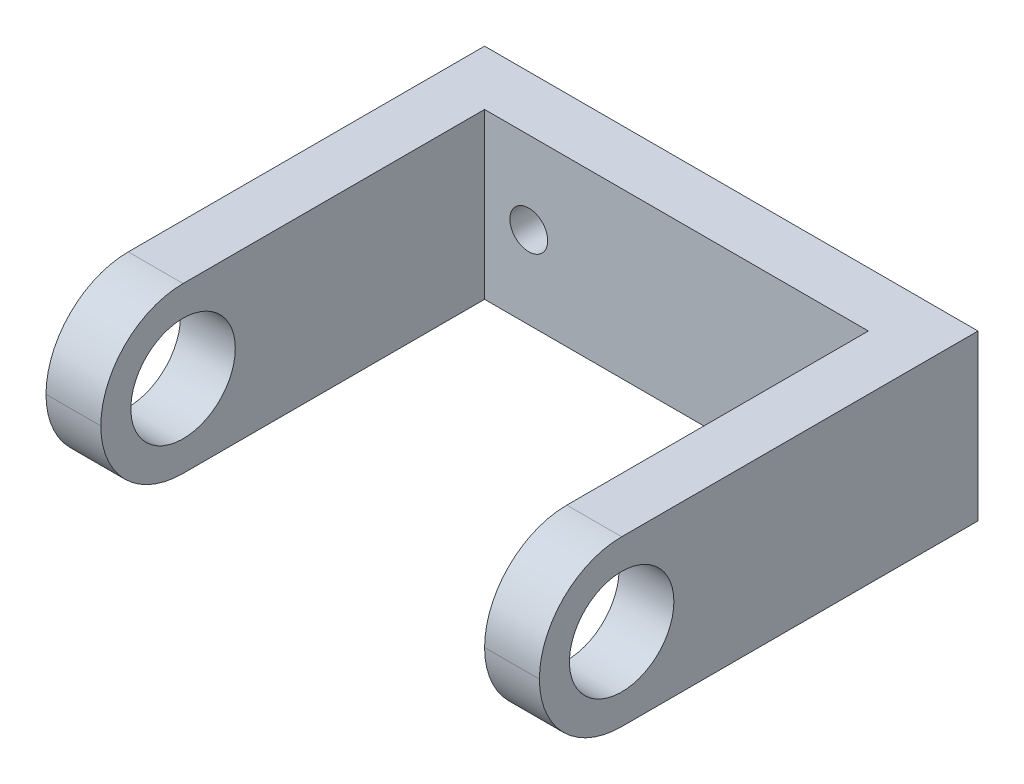
SolidWorks part; units mm, degrees
material "6061 Alloy"
ref_plane "Front Plane" through (0, 0, 0) normal (0, 0, 1) x (1, 0, 0)
ref_plane "Top Plane" through (0, 0, 0) normal (0, 1, 0) x (1, 0, 0)
ref_plane "Right Plane" through (0, 0, 0) normal (1, 0, 0) x (0, 0, -1)
sketch "Sketch1" plane through (0, 0, 0) normal (0, 1, 0) x (1, 0, 0)
  line L0 (-17.5, -7.5) -> (-22.5, -7.5)
  line L1 (-22.5, -7.5) -> (-22.5, 32.5)
  line L3 (-22.5, 32.5) -> (22.5, 32.5)
  line L5 (22.5, 32.5) -> (22.5, -7.5)
  line L6 (22.5, -7.5) -> (17.5, -7.5)
  line L7 (17.5, -7.5) -> (17.5, 27.5)
  line L9 (17.5, 27.5) -> (-17.5, 27.5)
  line L11 (-17.5, 27.5) -> (-17.5, -7.5)
  line L16 (0, 27.5) -> (0, 32.5) construction
  point P5 (0, 27.5)
  dimension "D1" = 5
  dimension "D2" = 35
  dimension "D3" = 27.5
  dimension "D6" = 7.5
extrude "Boss-Extrude1" add sketch "Sketch1" along normal mid plane 15
sketch "Sketch3" plane through (0, 0, 0) normal (1, 0, 0) x (0, 0, -1)
  circle A0 centre (0, 0) radius 4.7625
  dimension "D1" = 9.525
extrude "Cut-Extrude1" cut sketch "Sketch3" against normal through all both and the other way through all
fillet "Fillet1" radius 7.5 4 edges at (20, 7.5, 7.5) (20, -7.5, 7.5) (-20, -7.5, 7.5) (-20, 7.5, 7.5)
hole_wizard "#8-32 Tapped Hole1" positions "Sketch4" profile "Sketch5" tap size "#8-32" standard "ANSI Inch" end condition through all
sketch "Sketch4" plane through (0, 0, -27.5) normal (0, 0, 1) x (1, 0, 0)
  point P0 (-13.47, 0)
  dimension "D1" = 13.47
sketch "Sketch5" plane through (-13.47, 0, -27.5) normal (1, 0, 0) x (0, -1, 0)
  line L0 (0, 0) -> (0, 5)
  line L1 (0, 5) -> (1.7272, 5)
  line L2 (1.7272, 5) -> (1.7272, 0)
  line L5 (1.7272, 0) -> (0, 0)
  line L11 (0, -6.35) -> (0, 107.95) construction
  dimension "Thru Tap Drill Dia." = 3.4544
  dimension "Thru Tap Drill Depth" = 5
cosmetic thread "Hole Thread2" parameters "D2"=4.1656
